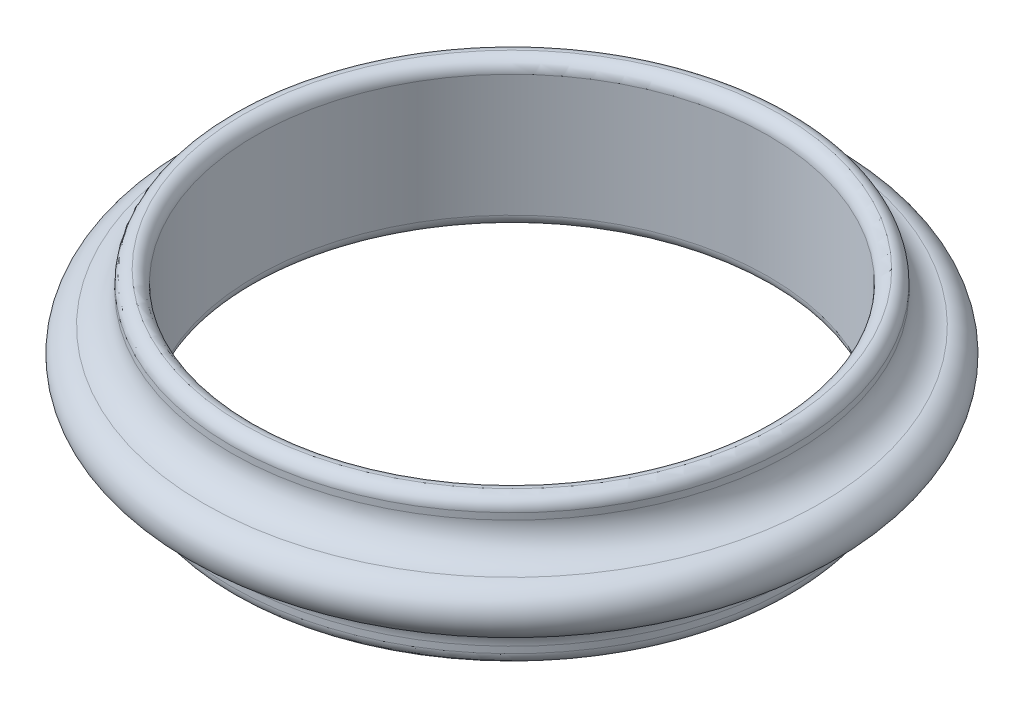
SolidWorks part; units mm, degrees
ref_plane "前视基准面" through (0, 0, 0) normal (0, 0, 1) x (1, 0, 0)
ref_plane "上视基准面" through (0, 0, 0) normal (0, 1, 0) x (1, 0, 0)
ref_plane "右视基准面" through (0, 0, 0) normal (1, 0, 0) x (0, 0, -1)
other "Configuration Table"
sketch "草图1" plane through (0, 0, 0) normal (0, 0, 1) x (1, 0, 0)
  line L0 (0, 18.7254) -> (0, -12.1955) construction
  line L1 (-23, 6) -> (-23, 4.4721)
  line L2 (-23, -4.4721) -> (-23, -6)
  line L3 (-23, 6) -> (-21, 6)
  line L4 (-21, 6) -> (-21, -6)
  line L5 (-21, -6) -> (-23, -6)
  arc A0 (-25.2222, 1.9876) -> (-25.2222, -1.9876) centre (-25, 0) ccw
  arc A1 (-25.2222, -1.9876) -> (-23, -4.4721) centre (-25.5, -4.4721) cw
  arc A2 (-25.2222, 1.9876) -> (-23, 4.4721) centre (-25.5, 4.4721) ccw
  point P10 (-23, 0)
  dimension "D1" = 4
  dimension "D4" = 2.5
  dimension "D2" = 25
  dimension "D3" = 23
  dimension "D5" = 2
  dimension "D6" = 12
  dimension "D7" = 6
revolve "旋转1" add sketch "草图1" angle 360 about L0
fillet "圆角1" radius 1 4 edges at (0, -6, 21) (0, -6, 23) (0, 6, 23) (0, 6, 21)
